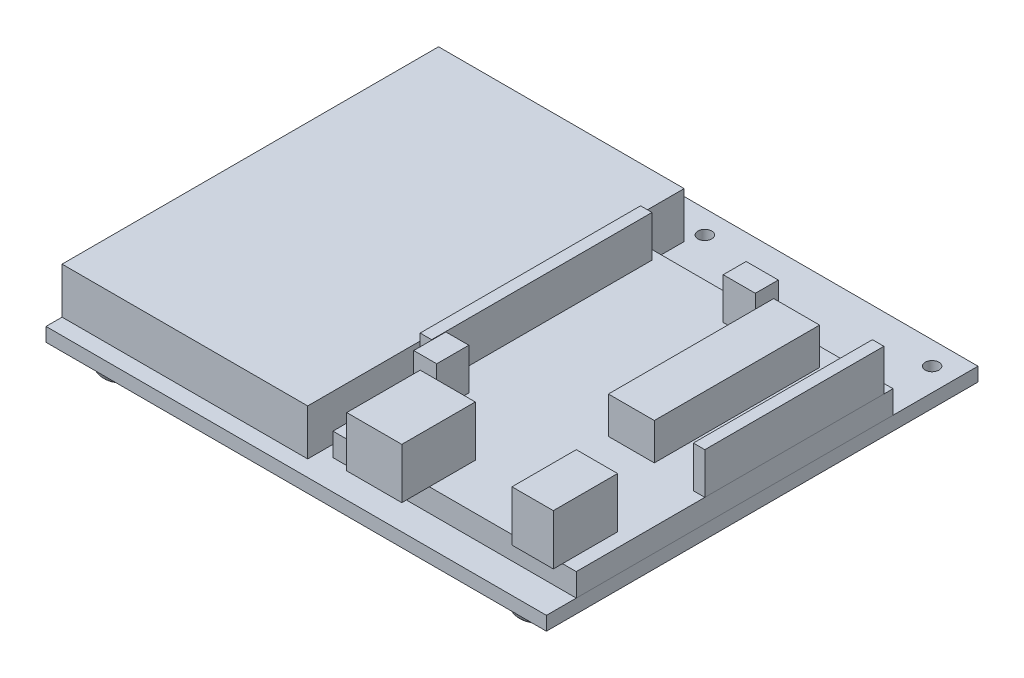
SolidWorks part; units mm, degrees
ref_plane "Front Plane" through (0, 0, 0) normal (0, 0, 1) x (1, 0, 0)
ref_plane "Top Plane" through (0, 0, 0) normal (0, 1, 0) x (1, 0, 0)
ref_plane "Right Plane" through (0, 0, 0) normal (1, 0, 0) x (0, 0, -1)
sketch "Sketch1" plane through (0, 0, 0) normal (0, 1, 0) x (1, 0, 0)
  line L0 (54.5, 94) -> (54.5, 0) construction
  line L1 (0, 0) -> (109, 0)
  line L2 (0, 0) -> (0, 94)
  line L3 (0, 94) -> (109, 94)
  line L4 (109, 0) -> (109, 94)
  circle A0 centre (104, 89) radius 1.5
  circle A1 centre (5, 89) radius 1.5
  circle A2 centre (54.5, 89) radius 1.5
  dimension "D3" = 3
  dimension "D4" = 3
  dimension "D1" = 109
  dimension "D2" = 94
  dimension "D5" = 5
  dimension "D6" = 5
extrude "Boss-Extrude1" add sketch "Sketch1" along normal blind 3
sketch "Sketch2" plane through (0, 3, 0) normal (0, 1, 0) x (1, 0, 0)
  line L0 (0, 94) -> (0, 0) construction
  line L1 (53.5, 3.5) -> (0, 3.5)
  line L2 (53.5, 3.5) -> (53.5, 85.5)
  line L3 (53.5, 85.5) -> (0, 85.5)
  line L4 (0, 3.5) -> (0, 85.5)
  line L5 (109, 0) -> (109, 94) construction
  line L6 (109, 75.5) -> (56, 75.5)
  line L7 (109, 75.5) -> (109, 6.5)
  line L8 (109, 6.5) -> (56, 6.5)
  line L9 (56, 75.5) -> (56, 6.5)
  line L10 (0, 0) -> (109, 0) construction
  line M7 (0, 94) -> (0, 0)
  line M9 (109, 0) -> (109, 94)
  dimension "D1" = 53.5
  dimension "D2" = 82
  dimension "D3" = 3.5
  dimension "D4" = 69
  dimension "D5" = 6.5
  dimension "D6" = 53
extrude "Boss-Extrude2" add sketch "Sketch2" along normal blind 10 separate body contours L2 L3 L1 M7 region at (26.75, 3, -44.5)
extrude "Boss-Extrude3" add sketch "Sketch2<3>" along normal blind 5 separate body contours L6 L9 L8 M9 region at (82.5, 3, -41)
sketch "Sketch2<3>" plane through (0, 3, 0) normal (0, 1, 0) x (1, 0, 0) same geometry as "Sketch2"
sketch "Sketch3" plane through (0, 8, 0) normal (0, 1, 0) x (1, 0, 0)
  line L0 (109, 6.5) -> (109, 75.5) construction
  line L1 (65, 16.5) -> (77, 16.5)
  line L2 (65, 16.5) -> (65, 0.5)
  line L3 (65, 0.5) -> (77, 0.5)
  line L4 (77, 16.5) -> (77, 0.5)
  line L5 (97, 18.5) -> (106, 18.5)
  line L6 (97, 18.5) -> (97, 4.5)
  line L7 (97, 4.5) -> (106, 4.5)
  line L8 (106, 18.5) -> (106, 4.5)
  line L9 (106.5, 73.5) -> (109, 73.5)
  line L10 (106.5, 73.5) -> (106.5, 34.5)
  line L11 (106.5, 34.5) -> (109, 34.5)
  line L12 (109, 73.5) -> (109, 34.5)
  line L13 (56, 75.5) -> (56, 6.5) construction
  line L14 (87, 71.5) -> (97, 71.5)
  line L15 (87, 71.5) -> (87, 35.5)
  line L16 (87, 35.5) -> (97, 35.5)
  line L17 (97, 71.5) -> (97, 35.5)
  line L18 (78, 74.5) -> (85, 74.5)
  line L19 (78, 74.5) -> (78, 69.5)
  line L20 (78, 69.5) -> (85, 69.5)
  line L21 (85, 74.5) -> (85, 69.5)
  line L22 (58.5, 73.5) -> (56, 73.5)
  line L23 (58.5, 73.5) -> (58.5, 25.5)
  line L24 (58.5, 25.5) -> (56, 25.5)
  line L25 (56, 73.5) -> (56, 25.5)
  line L27 (58.6, 28.5) -> (63.6, 28.5)
  line L28 (58.6, 28.5) -> (58.6, 21.5)
  line L29 (58.6, 21.5) -> (63.6, 21.5)
  line L30 (63.6, 28.5) -> (63.6, 21.5)
  line L32 (109, 75.5) -> (56, 75.5) construction
  line L33 (109, 6.5) -> (56, 6.5) construction
  line L34 (109, 75.5) -> (56, 75.5) construction
  line L35 (109, 6.5) -> (56, 6.5) construction
  line M19 (56, 75.5) -> (56, 6.5)
  line M20 (56, 6.5) -> (109, 6.5)
  line M21 (109, 6.5) -> (109, 75.5)
  dimension "D1" = 12
  dimension "D2" = 16
  dimension "D3" = 6
  dimension "D4" = 2.5
  dimension "D5" = 48
  dimension "D6" = 7
  dimension "D7" = 5
  dimension "D8" = 2
  dimension "D9" = 9
  dimension "D10" = 14
  dimension "D11" = 2
  dimension "D12" = 2.5
  dimension "D13" = 39
  dimension "D14" = 2
  dimension "D15" = 36
  dimension "D16" = 10
  dimension "D17" = 12
  dimension "D18" = 4
  dimension "D19" = 7
  dimension "D20" = 5
  dimension "D21" = 1
  dimension "D22" = 24
  dimension "D23" = 15
  dimension "D24" = 9
  dimension "D25" = 3
  dimension "D26" = 2.6
extrude "Boss-Extrude4" add sketch "Sketch3" along normal blind 9 separate body contours L24 L23 L22 M19 | L10 L11 L9 M21 | L21 L18 L19 L20 | L30 L27 L23 L28 L29 region at (107.75, 8, -54) region at (81.5, 8, -72) region at (57.25, 8, -49.5) region at (61.1, 8, -25)
extrude "Boss-Extrude5" add sketch "Sketch3<3>" along normal blind 8 contours L17 L14 L15 L16 region at (92, 8, -53.5)
sketch "Sketch3<3>" plane through (0, 8, 0) normal (0, 1, 0) x (1, 0, 0) same geometry as "Sketch3"
extrude "Boss-Extrude6" add sketch "Sketch3<4>" along normal blind 11 contours L4 L1 L2 M20 | L4 L2 L3 M20 | L8 L5 L6 M20 | L8 L6 L7 M20 region at (101.5, 8, -12.5) region at (101.5, 8, -5.5) region at (71, 8, -11.5) region at (71, 8, -3.5)
sketch "Sketch3<4>" plane through (0, 8, 0) normal (0, 1, 0) x (1, 0, 0) same geometry as "Sketch3"
sketch "Sketch4" plane through (0, 0, 0) normal (0, -1, 0) x (1, 0, 0)
  circle A0 centre (99.5849, -7.7445) radius 5
  circle A1 centre (9.0281, -7.7445) radius 5
  circle A2 centre (13.0641, -82.6388) radius 5
  circle A3 centre (96.9815, -82.6388) radius 5
  dimension "D1" = 10
  dimension "D2" = 10
  dimension "D3" = 10
  dimension "D4" = 10
extrude "Boss-Extrude8" add sketch "Sketch4" along normal blind 5
chamfer "Chamfer1" distance 5 angle 8 4 edges at (13.0641, -5, -87.6388) (9.0281, -5, -12.7445) (96.9815, -5, -87.6388) (99.5849, -5, -12.7445) first distance on face at (13.0641, -5, -87.6388) first distance on face at (9.0281, -5, -12.7445) first distance on face at (96.9815, -5, -87.6388) first distance on face at (99.5849, -5, -12.7445)
fillet "Fillet1" radius 2 4 edges at (99.5849, -5, -12.0418) (9.0281, -5, -12.0418) (13.0641, -5, -86.936) (96.9815, -5, -86.936) second distance 3 first distance on face at (99.5849, 0, -12.7445) first distance on face at (9.0281, 0, -12.7445) first distance on face at (13.0641, 0, -87.6388) first distance on face at (96.9815, 0, -87.6388)
equation "\"D4@Sketch1\"=\"D3@Sketch1\""
